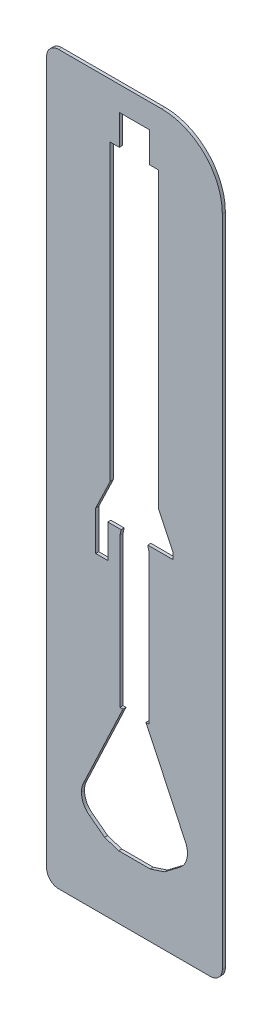
SolidWorks part; units mm, degrees
material "PETG"
ref_plane "Front Plane" through (0, 0, 0) normal (0, 0, 1) x (1, 0, 0)
ref_plane "Top Plane" through (0, 0, 0) normal (0, 1, 0) x (1, 0, 0)
ref_plane "Right Plane" through (0, 0, 0) normal (1, 0, 0) x (0, 0, -1)
other "Configuration Table"
sketch "Sketch11" plane through (0, 0, 0) normal (0, 0, 1) x (1, 0, 0)
  line L0 (0, 60) -> (0, -60) construction
  line L1 (-12.5, 60) -> (4.5, 60)
  line L2 (-14.5, 58) -> (-14.5, -58)
  line L3 (-12.5, -60) -> (12.5, -60)
  line L4 (14.5, 50) -> (14.5, -58)
  line L5 (-14.5, 60) -> (14.5, -60) construction
  line L6 (-14.5, -60) -> (14.5, 60) construction
  line L7 (-14.5, 0) -> (14.5, 0) construction
  line L8 (0, -55) -> (0, 55) construction
  arc A0 (-14.5, -58) -> (-12.5, -60) centre (-12.5, -58) ccw
  arc A1 (12.5, -60) -> (14.5, -58) centre (12.5, -58) ccw
  arc A2 (4.5, 60) -> (14.5, 50) centre (4.5, 50) cw
  arc A3 (-12.5, 60) -> (-14.5, 58) centre (-12.5, 58) ccw
  point P0 (0, 0)
extrude "Boss-Extrude5" add sketch "Sketch11" along normal blind 0.508
sketch "Sketch1" plane through (0, 0, 0.508) normal (0, 0, 1) x (1, 0, 0)
  line L26 (-2.5, 56) -> (2.5, 56)
  line L27 (-4, 2.5) -> (-6.4, -2.5)
  line L59 (2.5, 56) -> (2.5, 51)
  line L60 (2.5, 51) -> (4, 51)
  line L61 (4, 51) -> (4, 2.5)
  line L62 (4, 2.5) -> (6.4, -2.5)
  line L63 (6.4, -2.5) -> (6.4, -3.5)
  line L64 (6.4, -3.5) -> (2.2, -3.5)
  line L65 (2.2, -3.5) -> (2.4, -4.42)
  line L66 (2.4, -4.42) -> (2.4, -29)
  line L68 (-4, 2.5) -> (-4, 51)
  line L69 (-4, 51) -> (-2.5, 51)
  line L70 (-2.5, 51) -> (-2.5, 56)
  line L71 (-6.4, -2.5) -> (-6.4, -9)
  line L72 (-6.4, -9) -> (-4.4, -9)
  line L73 (-4.4, -9) -> (-4.4, -3.5)
  line L74 (-4.4, -3.5) -> (-2.2, -3.5)
  line L75 (-2.2, -3.5) -> (-2.4, -4.42)
  line L76 (-2.4, -4.42) -> (-2.4, -29)
  line L77 (-2.4, -29) -> (-1.9, -29)
  line L79 (2.4, -29) -> (1.9, -29)
  line L81 (-1.9, -29) -> (1.9, -29) construction
  line L82 (2.2, -3.5) -> (-2.2, -3.5) construction
  line L85 (-2.4, -4.42) -> (2.4, -4.42) construction
  line L87 (4, 2.5) -> (-4, 2.5) construction
  line L89 (-6.4, -2.5) -> (6.4, -2.5) construction
  line L91 (-2.5, 51) -> (2.5, 51) construction
  line L93 (8.375, -42.75) -> (1.9, -29) construction
  line L94 (4.925, -48.85) -> (7.4, -46.9731) construction
  line L95 (-7.4, -46.9731) -> (-4.925, -48.85) construction
  line L96 (-1.9, -29) -> (-8.375, -42.75) construction
  line L97 (8.375, -42.75) -> (1.9, -29)
  line L98 (4.925, -48.85) -> (7.4, -46.9731)
  line L99 (-7.4, -46.9731) -> (-4.925, -48.85)
  line L100 (-1.9, -29) -> (-8.375, -42.75)
  line L101 (-2.6, -49.6) -> (2.6, -49.6)
  line L102 (2.6, -49.6) -> (4.925, -48.85)
  line L104 (-4.925, -48.85) -> (-2.6, -49.6)
  line L106 (-12.5, -60) -> (12.5, -60) construction
  line L107 (0, 56) -> (0, -49.6) construction
  line L109 (4.5, 60) -> (-12.5, 60) construction
  line L110 (0, -49.6) -> (0, -60) construction
  spline S0 degree 3 poles (-2211.0014, 1964.9254) (1967.9153, -2344.8373) (-1653.2812, 2485.386) (1333.8003, -2728.018) knots -35.229961 -35.229961 -35.229961 -35.229961 41.331958 41.331958 41.331958 41.331958 only from (8.75, -44.3) to (8.375, -42.75) construction
  spline S1 degree 3 poles (1576.4055, 2503.5485) (-1886.2128, -2403.2166) (2181.5396, 2053.8609) (-2397.4558, -1825.6873) knots -16.257706 -16.257706 -16.257706 -16.257706 22.929369 22.929369 22.929369 22.929369 only from (7.4, -46.9731) to (8.75, -44.3) construction
  spline S2 degree 3 poles (2397.5108, -1825.734) (-2181.5509, 2053.8785) (1886.1887, -2403.1947) (-1576.357, 2503.4798) knots -15.931221 -15.931221 -15.931221 -15.931221 23.255828 23.255828 23.255828 23.255828 only from (-8.75, -44.3) to (-7.4, -46.9731) construction
  spline S3 degree 3 poles (-1333.8598, -2728.1219) (1653.3192, 2485.4325) (-1967.9185, -2344.8332) (2210.959, 1964.8816) knots -36.332467 -36.332467 -36.332467 -36.332467 40.229701 40.229701 40.229701 40.229701 only from (-8.375, -42.75) to (-8.75, -44.3) construction
  spline S4 degree 3 poles (8.75, -44.3) (8.7497, -43.7369) (8.614, -43.206) (8.375, -42.75) knots 2 2 2 2 3 3 3 3
  spline S5 degree 3 poles (7.4, -46.9731) (8.2114, -46.4163) (8.7506, -45.4277) (8.75, -44.3) knots 3 3 3 3 3.998305 3.998305 3.998305 3.998305
  spline S6 degree 3 poles (-8.75, -44.3) (-8.7506, -45.4277) (-8.2114, -46.4163) (-7.4, -46.9731) knots 3 3 3 3 3.998305 3.998305 3.998305 3.998305
  spline S7 degree 3 poles (-8.375, -42.75) (-8.614, -43.206) (-8.7497, -43.7369) (-8.75, -44.3) knots 2 2 2 2 3 3 3 3
  point P40 (4.3, -3.5)
  dimension "D7" = 25.5
  dimension "D8" = 5
  dimension "D10" = 5.5
  dimension "D11" = 2
  dimension "D12" = 2
  dimension "D1" = 10.4
  dimension "D6" = 5
  dimension "D17" = 3.8
  dimension "D14" = 4.8
  dimension "D4" = 5
  dimension "D2" = 5.2
  dimension "D3" = 4
  dimension "D5" = 8
  dimension "D9" = 1
  dimension "D13" = 4.4
  dimension "D15" = 0.92
  dimension "D16" = 12.8
extrude "Cut-Extrude1" cut sketch "Sketch1" against normal through all contours L70 L26 L59 L60 L61 L62 L63 L64 L65 L66 L79 L97 S4 S5 L98 L102 L101 L104 L99 S6 S7 L100 L77 L76 L75 L74 L73 L72 L71 L27 L68 L69
chamfer "Chamfer1" distance 0.5 angle 15 rebuild error yes
sketch "Sketch12" [suppressed] plane through (0, 0, 0.508) normal (0, 0, 1) x (1, 0, 0)
  line L0 (2.5859, -25.5799) -> (6.197, -37.5) construction
  line L2 (-2.5, -25) -> (-2.5, -4.4) construction
  line L3 (2.5, -25) -> (2.5, -4.4) construction
  line L4 (2.5, -4.4) -> (2.325, -3.5) construction
  line L7 (-2.5, -4.4) -> (-2.325, -3.5) construction
  line L8 (2.5859, -25.5799) -> (6.197, -37.5) construction
  line L9 (-2.4, -25) -> (-2.4, -4.4096) construction
  line L10 (-2.5, -25) -> (-2.5, -4.4)
  line L11 (2.5, -25) -> (2.5, -4.4)
  line L12 (2.5, -4.4) -> (2.325, -3.5)
  line L15 (-2.5, -4.4) -> (-2.325, -3.5)
  line L16 (-2.4, -24.325) -> (-2.4, -4.4096)
  line L17 (-2.4, -4.4096) -> (-2.2, -3.5)
  line L18 (-2.4, -4.4096) -> (-2.2268, -3.5191) construction
  line L19 (0, 0) -> (0, -25.5799) construction
  line L20 (2.2, -3.5) -> (2.4, -4.4)
  line L21 (2.4, -24.325) -> (2.4, -4.4)
  line L22 (-6.197, -37.5) -> (-2.5859, -25.5799) construction
  line L23 (2.4, -25) -> (2.4, -4.4) construction
  line L24 (-2.2, -3.5) -> (2.2, -3.5) construction
  line L25 (-2.2, -3.5) -> (-2.325, -3.5)
  line L26 (2.325, -3.5) -> (2.2, -3.5)
  arc A2 (2.5, -25) -> (2.5859, -25.5799) centre (4.5, -25) ccw construction
  arc A3 (-2.5859, -25.5799) -> (-2.5, -25) centre (-4.5, -25) ccw construction
  arc A6 (2.5, -25) -> (2.5859, -25.5799) centre (4.5, -25) ccw
  arc A7 (-2.5859, -25.5799) -> (-2.5, -25) centre (-4.5, -25) ccw
  arc A8 (-2.5859, -25.5799) -> (-2.4, -24.325) centre (-6.7282, -24.325) ccw
  arc A9 (2.4, -24.325) -> (2.5859, -25.5799) centre (6.7282, -24.325) ccw
  point P32 (0, -3.5)
  dimension "D3" = 4.4
  dimension "D1" = 0.1
  dimension "D2" = 0.1
extrude "Boss-Extrude6" [suppressed] add sketch "Sketch12" against normal up to surface (0.508 mm away) up to face at (-0.7929, -0.7929, 0)
